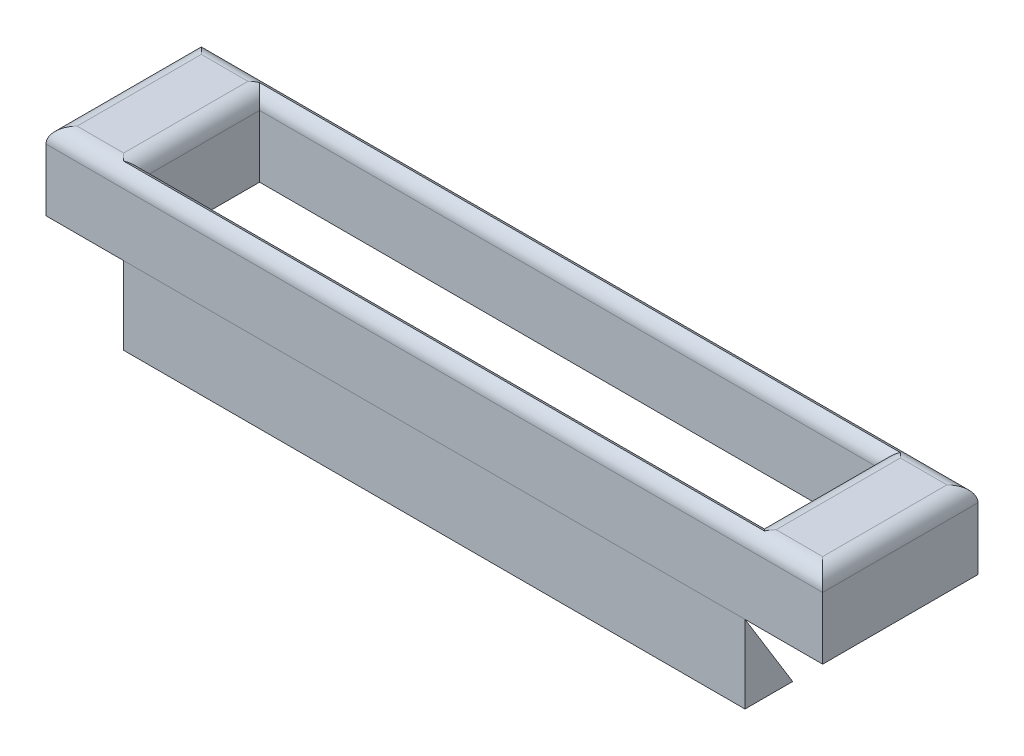
SolidWorks part; units mm, degrees
ref_plane "Front Plane" through (0, 0, 0) normal (0, 0, 1) x (1, 0, 0)
ref_plane "Top Plane" through (0, 0, 0) normal (0, 1, 0) x (1, 0, 0)
ref_plane "Right Plane" through (0, 0, 0) normal (1, 0, 0) x (0, 0, -1)
sketch "Sketch1" plane through (0, 0, 0) normal (0, 1, 0) x (1, 0, 0)
  line L1 (-50, -1.1953) -> (50, -1.1953)
  line L2 (-50, -1.1953) -> (-50, 18.8047)
  line L3 (-50, 18.8047) -> (50, 18.8047)
  line L4 (50, -1.1953) -> (50, 18.8047)
  line L5 (-50, -1.1953) -> (50, 18.8047) construction
  line L6 (-50, 18.8047) -> (50, -1.1953) construction
  point P0 (0, 0)
  dimension "D1" = 100
  dimension "D2" = 20
extrude "Boss-Extrude1" add sketch "Sketch1" along normal blind 10 and the other way blind 10
sketch "Sketch2" plane through (50, 0, 0) normal (1, 0, 0) x (0, 0, -1)
  line L0 (-1.1953, 0) -> (18.8047, 0)
  line L1 (18.8047, 0) -> (18.8047, -10)
  line L2 (18.8047, -10) -> (-1.1953, 0)
extrude "Cut-Extrude1" cut sketch "Sketch2" against normal up to surface (100 mm away) up to face at (-50, 0, -8.8047)
sketch "Sketch3" plane through (0, 10, 0) normal (0, 1, 0) x (1, 0, 0)
  line L0 (50, 18.8047) -> (-50, 18.8047) construction
  line L5 (-40, 16.3047) -> (40, 16.3047)
  line L6 (-40, 16.3047) -> (-40, 1.3047)
  line L7 (-40, 1.3047) -> (40, 1.3047)
  line L8 (40, 16.3047) -> (40, 1.3047)
  line L9 (-40, 16.3047) -> (40, 1.3047) construction
  line L10 (-40, 1.3047) -> (40, 16.3047) construction
  point P0 (-37.1935, 10.2161)
  dimension "D1" = 80
  dimension "D2" = 15
  dimension "D3" = 2.5
extrude "Cut-Extrude2" cut sketch "Sketch3" against normal up to surface (10 mm away) up to face at (0, 0, -8.8047)
fillet "Fillet3" radius 2 8 edges at (0, 10, 1.1953) (-50, 10, -8.8047) (0, 10, -18.8047) (50, 10, -8.8047) (-40, 10, -8.8047) (0, 10, -1.3047) (40, 10, -8.8047) (0, 10, -16.3047)
sketch "Sketch4" plane through (-50, 0, 0) normal (-1, 0, 0) x (0, 0, 1)
  line L0 (1.1953, -10) -> (1.1953, 0)
  line L1 (1.1953, 0) -> (-18.8047, -10)
  line L2 (-18.8047, -10) -> (1.1953, -10)
extrude "Cut-Extrude4" cut sketch "Sketch4" against normal blind 10
sketch "Sketch5" plane through (50, 0, 0) normal (1, 0, 0) x (0, 0, -1)
  line L0 (-1.1953, -10) -> (-1.1953, 0)
  line L1 (-1.1953, 0) -> (18.8047, -10)
  line L2 (18.8047, -10) -> (-1.1953, -10)
extrude "Cut-Extrude5" cut sketch "Sketch5" against normal blind 10
sketch "Sketch6" plane through (-40, 0, 0) normal (-1, 0, 0) x (0, 0, 1)
  line L0 (1.1953, 0) -> (-4.9444, -10)
  line L1 (-4.9444, -10) -> (-18.8047, -10)
  line L2 (-18.8047, -10) -> (1.1953, 0)
  point P2 (-4.9444, -10)
extrude "Cut-Extrude6" cut sketch "Sketch6" against normal up to surface (80 mm away) up to face at (40, -6.6667, -5.4713)
sketch "Sketch7" plane through (-40, 0, 0) normal (-1, 0, 0) x (0, 0, 1)
  line L0 (-8.8047, -10) -> (-8.8047, 0)
  line L1 (-8.8047, 0) -> (1.1953, 0)
  line L2 (1.1953, 0) -> (-8.8047, -10)
sketch "Sketch8" plane through (0, -0.533, 0.8681) normal (0, 0.5232, -0.8522) x (1, 0, 0)
  circle A0 centre (0, 6.3306) radius 2
